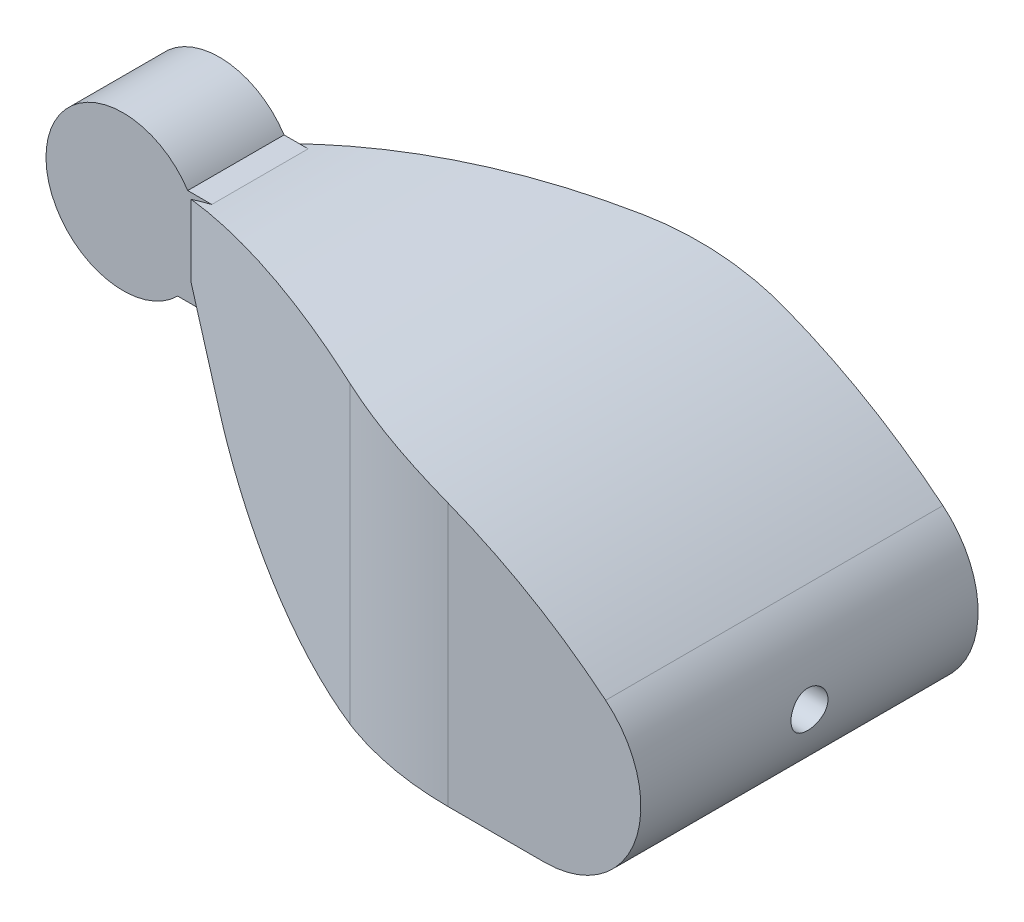
SolidWorks part; units mm, degrees
note: The reader was unsure of these and kept them because the rebuilt part matched: shared geometry of "Sketch33<2>".
material "Polycarbonate"
ref_plane "Front Plane" through (0, 0, 0) normal (0, 0, 1) x (1, 0, 0)
ref_plane "Top Plane" through (0, 0, 0) normal (0, 1, 0) x (1, 0, 0)
ref_plane "Right Plane" through (0, 0, 0) normal (1, 0, 0) x (0, 0, -1)
sketch "Sketch2" plane through (0, 0, 0) normal (0, 0, 1) x (1, 0, 0)
  line L0 (4.4873, -2.3813) -> (4.4873, 2.3813)
  arc A0 (4.4873, 2.3813) -> (4.4873, -2.3813) centre (0, 0) ccw
  dimension "D1" = 10.16
  dimension "D2" = 4.7625
extrude "Boss-Extrude1" add sketch "Sketch2" along normal blind 6.35
sketch "Sketch3" plane through (0, 0, 0) normal (0, 0, 1) x (1, 0, 0)
  line L1 (2.2669, 9.525) -> (39.7391, 9.525) construction
  line L4 (39.7391, 9.525) -> (39.7391, -4.6159) construction
  line L6 (4.4873, 2.3813) -> (4.4873, -2.3813)
  line L8 (35.7113, -15.875) -> (21.9011, -15.875)
  line L12 (4.4873, -2.3813) -> (7.4648, -7.5394)
  arc A0 (4.4873, 2.3813) -> (4.4873, -2.3813) centre (0, 0) ccw construction
  arc A1 (4.4873, 2.3813) -> (4.4873, -2.3813) centre (0, 0) ccw construction
  arc A4 (7.4648, -7.5394) -> (21.9011, -15.875) centre (21.9011, 0.7938) ccw
  arc A5 (39.7391, -4.6159) -> (35.7113, -15.875) centre (35.7113, -9.525) cw
  arc A6 (4.4873, 2.3813) -> (39.7391, -4.6159) centre (15.5723, -34.0705) cw
  dimension "D5" = 16.6687
  dimension "D6" = 6.35
  dimension "D7" = 38.1
  dimension "D4" = 5.9558
  dimension "D1" = 25.4
  dimension "D2" = 13.8102
  dimension "D3" = 9.525
extrude "Boss-Extrude3" add sketch "Sketch3" along normal offset from surface (22.225 mm away) 7.9375 from offset 7.9375 up to face at (-0.2963, 0, 6.35) offset beyond the face yes offset against normal yes
sketch "Sketch14" plane through (0, 0, 0) normal (0, 1, 0) x (1, 0, 0)
  line L0 (4.4873, -14.2875) -> (4.4873, -6.35) construction
  line L1 (4.4873, -6.35) -> (4.4873, 0) construction
  line L2 (4.4873, -6.35) -> (21.4281, -12.8234)
  line L3 (4.4873, 0) -> (21.4281, 6.4734)
  line L4 (39.7391, 7.9375) -> (4.4873, 7.9375) construction
  line L5 (4.4873, -3.175) -> (42.0613, -3.175) construction
  line L6 (-5.08, -6.35) -> (4.4873, -6.35) construction
  line L10 (4.4873, -6.35) -> (4.4873, -14.2875)
  line L11 (4.4873, -14.2875) -> (29.3613, -14.2875)
  line L12 (4.4873, 0) -> (4.4873, 7.9375)
  line L13 (4.4873, 7.9375) -> (29.3613, 7.9375)
  line L16 (4.4873, -14.2875) -> (39.7391, -14.2875) construction
  line L17 (4.4873, -6.35) -> (4.4873, 0) construction
  line L18 (42.0613, 7.9375) -> (35.7113, 7.9375) construction
  line L19 (42.0613, 7.9375) -> (35.7113, 7.9375) construction
  arc A0 (21.4281, -12.8234) -> (29.3613, -14.2875) centre (29.3613, 7.9375) ccw
  arc A1 (21.4281, 6.4734) -> (29.3613, 7.9375) centre (29.3613, -14.2875) cw
  point P13 (4.4873, -3.175)
  dimension "D1" = 12.7
extrude "Cut-Extrude4" cut sketch "Sketch14" against normal through all both and the other way through all
ref_plane "Plane2" through (0, 0, 3.175) normal (0, 0, -1) x (-1, 0, 0)
ref_plane "Plane4" through (42.0613, 0, 0) normal (1, 0, 0) x (0, 0, -1)
sketch "Sketch16" plane through (42.0613, 0, 0) normal (1, 0, 0) x (0, 0, -1)
  line L0 (-14.2875, -15.875) -> (7.9375, -15.875) construction
  line L1 (-14.2875, -15.875) -> (7.9375, -15.875) construction
  line L3 (-5.5563, -7.2009) -> (-0.7938, -7.2009)
  line L4 (-5.5563, -7.2009) -> (-5.5563, -11.9634)
  line L5 (-5.5563, -11.9634) -> (-0.7938, -11.9634)
  line L6 (-0.7938, -7.2009) -> (-0.7938, -11.9634)
  line L7 (-5.5563, -7.2009) -> (-0.7938, -11.9634) construction
  line L8 (-5.5563, -11.9634) -> (-0.7938, -7.2009) construction
  line L9 (-14.2875, -4.6159) -> (7.9375, -4.6159) construction
  point P2 (-3.175, -9.5821)
  point P13 (-3.175, -4.6159)
  dimension "D1" = 4.7625
  dimension "D2" = 3.9116
sketch "Sketch25" plane through (0, 0, 6.35) normal (0, 0, 1) x (1, 0, 0)
  line L0 (7.4648, -7.5394) -> (4.4873, -2.3813) construction
  line L1 (5.1838, -3.5879) -> (4.4873, -2.3813)
  line L2 (5.1838, -3.5879) -> (3.5963, -3.5879)
  line L3 (4.26, 2.7675) -> (5.8475, 2.7675)
  arc A1 (4.4873, 2.3813) -> (4.4873, -2.3813) centre (0, 0) ccw construction
  arc A3 (4.4873, 2.3813) -> (4.26, 2.7675) centre (0, 0) ccw
  arc A4 (3.5963, -3.5879) -> (4.4873, -2.3813) centre (0, 0) ccw
  arc A6 (21.4281, 3.5768) -> (4.4873, 2.3813) centre (15.5723, -34.0705) ccw construction
  arc A7 (5.8475, 2.7675) -> (4.4873, 2.3813) centre (15.5723, -34.0705) ccw
  dimension "D1" = 1.5875
  dimension "D2" = 1.5875
extrude "Cut-Extrude10" cut sketch "Sketch16" against normal through all from offset 19.05 offset against normal yes
sketch "Sketch29" plane through (0, 0, 3.175) normal (0, 0, -1) x (-1, 0, 0)
  line L0 (-23.0113, -7.2009) -> (-6.4321, -5.7504)
  line L1 (-23.0113, -11.9634) -> (-13.5493, -13.6318)
  line L2 (-7.4648, -7.5394) -> (-4.4873, -2.3812) construction
  line L3 (-7.2694, -7.2009) -> (-6.4321, -5.7504)
  line L4 (-23.0113, -11.9634) -> (-11.1725, -11.9634)
  line L5 (-23.0113, -7.2009) -> (-23.0113, -11.9634)
  line L6 (-7.2694, -7.2009) -> (-23.0113, -7.2009)
  line L7 (-7.4648, -7.5394) -> (-7.2694, -7.2009)
  line L8 (-23.0113, -11.9634) -> (-11.1725, -11.9634)
  line L9 (-23.0113, -7.2009) -> (-23.0113, -11.9634)
  line L10 (-7.2694, -7.2009) -> (-23.0113, -7.2009)
  arc A0 (-21.4281, -15.8683) -> (-7.4648, -7.5394) centre (-21.9011, 0.7938) ccw construction
  arc A1 (-11.1725, -11.9634) -> (-7.4648, -7.5394) centre (-21.9011, 0.7938) ccw
  arc A3 (-13.5493, -13.6318) -> (-11.1725, -11.9634) centre (-21.9011, 0.7938) ccw
  dimension "D2" = 5
  dimension "D3" = 10
  dimension "D1" = 0
extrude "Cut-Extrude11" cut sketch "Sketch29" against normal up to surface and the other way up to surface contours L10 L3 L0 | L1 A3 L8 up to face at (14.3472, -9.2059, 5.5562) other way up to face at (14.3472, -9.2059, 0.7938)
hole_wizard "#2 Clearance Hole1" positions "Sketch30" profile "Sketch31" hole size "#2" standard "ANSI Inch" end condition through all
sketch "Sketch30" plane through (23.0113, 0, 0) normal (-1, 0, 0) x (0, 0, 1)
  line L0 (0.7938, -7.2009) -> (5.5563, -7.2009) construction
  line L1 (0.7938, -11.9634) -> (0.7938, -7.2009) construction
  point P0 (3.175, -9.5821)
  point P5 (3.175, -7.2009)
  point P8 (0.7938, -9.5821)
sketch "Sketch31" plane through (23.0113, -9.5821, 3.175) normal (0, 1, 0) x (0, 0, 1)
  line L0 (0, 0) -> (0, 19.05)
  line L1 (0, 19.05) -> (1.2192, 19.05)
  line L2 (1.2192, 19.05) -> (1.2192, 0)
  line L5 (1.2192, 0) -> (0, 0)
  line L11 (0, -6.35) -> (0, 107.95) construction
  dimension "Thru Hole Dia." = 2.4384
  dimension "Thru Hole Depth" = 19.05
extrude "Boss-Extrude19" add sketch "Sketch25" against normal up to surface (6.35 mm away) up to face at (-0.2963, 0, 0)
sketch "Sketch32" plane through (0, 0, 3.175) normal (0, 0, -1) x (-1, 0, 0)
  line L0 (-29.3613, -15.875) -> (-21.9011, -15.875) construction
  line L1 (-35.7113, -15.875) -> (-29.3613, -15.875) construction
  line L2 (-29.3613, -15.875) -> (-21.9011, -15.875)
  line L3 (-35.7113, -15.875) -> (-29.3613, -15.875)
  line L4 (-40.2014, -14.0151) -> (-39.0789, -12.8926)
  line L5 (-13.5493, -13.6318) -> (-16.1932, -13.1656)
  line L6 (-35.7113, -14.2875) -> (-21.9011, -14.2875)
  arc A0 (-21.4281, -15.8683) -> (-7.4648, -7.5394) centre (-21.9011, 0.7938) ccw construction
  arc A1 (-21.9011, -15.875) -> (-21.4281, -15.8683) centre (-21.9011, 0.7938) ccw construction
  arc A2 (-39.7391, -4.6159) -> (-35.7113, -15.875) centre (-35.7113, -9.525) ccw construction
  arc A3 (-21.4281, -15.8683) -> (-13.5493, -13.6318) centre (-21.9011, 0.7938) ccw
  arc A4 (-21.9011, -15.875) -> (-21.4281, -15.8683) centre (-21.9011, 0.7938) ccw
  arc A5 (-40.2014, -14.0151) -> (-35.7113, -15.875) centre (-35.7113, -9.525) ccw
  arc A6 (-21.9011, -14.2875) -> (-16.1932, -13.1656) centre (-21.9011, 0.7938) ccw
  arc A7 (-35.7113, -14.2875) -> (-39.0789, -12.8926) centre (-35.7113, -9.525) cw
  dimension "D2" = 45
  dimension "D3" = 1.5875
  dimension "D1" = 10
extrude "Cut-Extrude12" cut sketch "Sketch32" against normal blind 4.7625 and the other way blind 4.7625
sketch "Sketch33" plane through (0, 0, 7.9375) normal (0, 0, -1) x (-1, 0, 0)
  line L0 (-21.9011, -15.875) -> (-21.9011, -14.2875)
  line L4 (-13.5493, -13.6318) -> (-16.1932, -13.1656)
  line L5 (-21.9011, -14.2875) -> (-35.7113, -14.2875)
  line L6 (-39.0789, -12.8926) -> (-40.2014, -14.0151)
  line L7 (-35.7113, -15.875) -> (-21.9011, -15.875)
  line L9 (-21.9011, -14.2875) -> (-35.7113, -14.2875)
  line L10 (-39.0789, -12.8926) -> (-40.2014, -14.0151)
  line L11 (-35.7113, -15.875) -> (-21.9011, -15.875)
  arc A4 (-21.9011, -15.875) -> (-13.5493, -13.6318) centre (-21.9011, 0.7938) ccw
  arc A5 (-21.9011, -14.2875) -> (-16.1932, -13.1656) centre (-21.9011, 0.7938) ccw
  arc A6 (-39.0789, -12.8926) -> (-35.7113, -14.2875) centre (-35.7113, -9.525) ccw
  arc A7 (-40.2014, -14.0151) -> (-35.7113, -15.875) centre (-35.7113, -9.525) ccw
  arc A10 (-39.0789, -12.8926) -> (-35.7113, -14.2875) centre (-35.7113, -9.525) ccw
  arc A11 (-40.2014, -14.0151) -> (-35.7113, -15.875) centre (-35.7113, -9.525) ccw
  dimension "D1" = 0
extrude "Cut-Extrude13" cut sketch "Sketch33" against normal blind 3.175
extrude "Cut-Extrude14" cut sketch "Sketch33<2>" along normal blind 3.175 from surface at 9.525
sketch "Sketch33<2>" plane through (0, 0, 7.9375) normal (0, 0, -1) x (-1, 0, 0) same geometry as "Sketch33"
